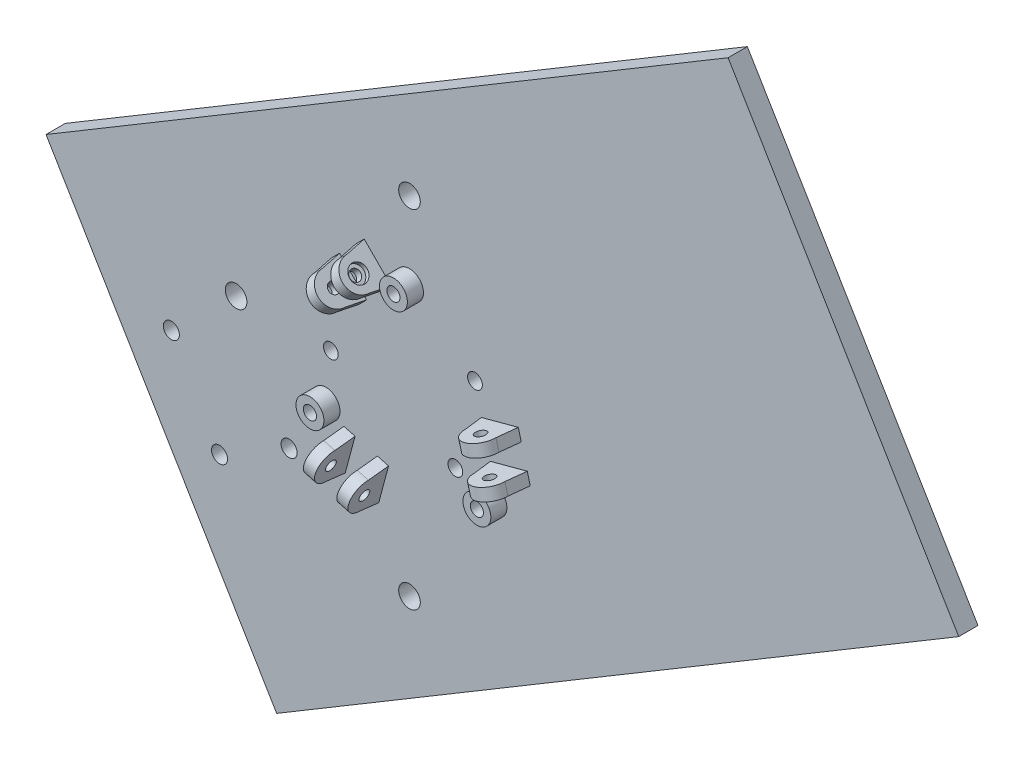
SolidWorks part; units mm, degrees
ref_plane "Front Plane" through (0, 0, 0) normal (0, 0, 1) x (1, 0, 0)
ref_plane "Top Plane" through (0, 0, 0) normal (0, 1, 0) x (1, 0, 0)
ref_plane "Right Plane" through (0, 0, 0) normal (1, 0, 0) x (0, 0, -1)
sketch "S01 - Rounded V3 backplate with cage and cassette fixings" plane through (0, 0, 0) normal (0, 0, 1) x (1, 0, 0)
  line L0 (-113.1634, 13.9297) -> (41.3567, 106.2526)
  line L5 (-113.1634, 13.9297) -> (-41.3567, -106.2526)
  line L7 (-41.3567, -106.2526) -> (113.1634, -13.9297)
  line L8 (-113.1634, 13.9297) -> (113.1634, -13.9297) construction
  line L9 (41.3567, 106.2526) -> (-41.3567, -106.2526) construction
  line L10 (41.3567, 106.2526) -> (99.1896, 140.8067)
  line L11 (99.1896, 140.8067) -> (170.9963, 20.6243)
  line L12 (170.9963, 20.6243) -> (113.1634, -13.9297)
  circle A7 centre (0, 54) radius 3.3651
  circle A8 centre (-53.9735, 0) radius 3.3651
  circle A9 centre (0, -54) radius 3.3651
  circle A10 centre (14.2762, -12.2367) radius 2.2944
  circle A11 centre (20.3946, 14.2762) radius 2.2944
  circle A12 centre (-24.4735, 0) radius 2.2944
  point P1 (0, 0)
  point P3 (0, 0)
  dimension "D2" = 180
  dimension "D3" = 54
  dimension "D4" = 6.7302
  dimension "D5" = 4.5888
  dimension "D6" = 20.3946
  dimension "D7" = 14.2762
  dimension "D8" = 4.5888
  dimension "D9" = 14.2762
  dimension "D10" = 12.2367
  dimension "D11" = 24.4735
  dimension "D12" = 4.5888
  dimension "D13" = 29.5
  dimension "D14" = 6.7302
  dimension "D16" = 6.7302
  dimension "D15" = 54
  dimension "D17" = 140
  dimension "D18" = 113.1634
  dimension "D19" = 106.2526
  dimension "D20" = 67.3693
extrude "01 - Rounded V3 backplate with cage and cassette fixings" add sketch "S01 - Rounded V3 backplate with cage and cassette fixings" along normal blind 6 from offset 12 offset against normal yes
sketch "S02 - Three cord guide pedestals" plane through (0, 0, 0) normal (0, 0, 1) x (1, 0, 0)
  circle A0 centre (25.9808, -15) radius 4.35
  circle A1 centre (0, 30) radius 4.35
  circle A2 centre (-25.9808, -15) radius 4.35
  dimension "D1" = 8.7
  dimension "D2" = 8.7
  dimension "D3" = 8.7
  dimension "D4" = 25.9808
  dimension "D5" = 25.9808
  dimension "D6" = 30
  dimension "D7" = 15
extrude "02 - Three cord guide pedestals" add sketch "S02 - Three cord guide pedestals" along normal blind 5 from offset 6 offset against normal yes
sketch "S03 - Three smooth grommet seats" plane through (0, 0, 0) normal (0, 0, 1) x (1, 0, 0)
  circle A0 centre (25.9808, -15) radius 2.05
  circle A1 centre (0, 30) radius 2.05
  circle A2 centre (-25.9808, -15) radius 2.05
  dimension "D1" = 4.1
  dimension "D2" = 4.1
  dimension "D3" = 4.1
  dimension "D4" = 25.9808
  dimension "D5" = 25.9808
  dimension "D6" = 30
  dimension "D7" = 15
extrude "03 - Three smooth grommet seats" cut sketch "S03 - Three smooth grommet seats" along normal blind 14 from offset 13 offset against normal yes
sketch3d "Plane points - Integral A1 fork cheek L"
  point P0 (30, 0, 0)
  point P1 (12.6133, -4.6587, 0)
  point P2 (30, 0, 18)
ref_plane "Drilling plane - Integral A1 fork cheek L" through (2.0096, -7.5, 0) normal (-0.2588, 0.9659, 0) x (0.9659, 0.2588, 0)
sketch "S04 - Integral A1 fork cheek L" plane through (2.0096, -7.5, 0) normal (-0.2588, 0.9659, 0) x (0.9659, 0.2588, 0)
  line L0 (35.0778, 7) -> (22.8778, 7)
  line L1 (22.8778, 7) -> (24.0278, 0)
  line L2 (33.9278, 0) -> (35.0778, 7)
  arc A0 (24.0278, 0) -> (33.9278, 0) centre (28.9778, 0) ccw
  dimension "D1" = 4.95
  dimension "D2" = 22.8778
  dimension "D3" = 28.9778
  dimension "D4" = 35.0778
  dimension "D5" = 7
extrude "04 - Integral A1 fork cheek L" add sketch "S04 - Integral A1 fork cheek L" along normal blind 3.6 from offset 7.2 offset against normal yes
sketch3d "Plane points - Integral A1 fork cheek R"
  point P0 (30, 0, 0)
  point P1 (12.6133, -4.6587, 0)
  point P2 (30, 0, 18)
ref_plane "Drilling plane - Integral A1 fork cheek R" through (2.0096, -7.5, 0) normal (-0.2588, 0.9659, 0) x (0.9659, 0.2588, 0)
sketch "S05 - Integral A1 fork cheek R" plane through (2.0096, -7.5, 0) normal (-0.2588, 0.9659, 0) x (0.9659, 0.2588, 0)
  line L0 (35.0778, 7) -> (22.8778, 7)
  line L1 (22.8778, 7) -> (24.0278, 0)
  line L2 (33.9278, 0) -> (35.0778, 7)
  arc A0 (24.0278, 0) -> (33.9278, 0) centre (28.9778, 0) ccw
  dimension "D1" = 4.95
  dimension "D2" = 22.8778
  dimension "D3" = 28.9778
  dimension "D4" = 35.0778
  dimension "D5" = 7
extrude "05 - Integral A1 fork cheek R" add sketch "S05 - Integral A1 fork cheek R" along normal blind 3.6 from offset 3.6
sketch3d "Plane points - A1 pivot through both cheeks"
  point P0 (30, 0, 0)
  point P1 (12.6133, -4.6587, 0)
  point P2 (30, 0, 18)
ref_plane "Drilling plane - A1 pivot through both cheeks" through (2.0096, -7.5, 0) normal (-0.2588, 0.9659, 0) x (0.9659, 0.2588, 0)
sketch "S06 - A1 pivot through both cheeks" plane through (2.0096, -7.5, 0) normal (-0.2588, 0.9659, 0) x (0.9659, 0.2588, 0)
  circle A0 centre (28.9778, 0) radius 1.65
  dimension "D1" = 3.3
  dimension "D2" = 28.9778
extrude "06 - A1 pivot through both cheeks" cut sketch "S06 - A1 pivot through both cheeks" along normal blind 15 from offset 7.5 offset against normal yes
sketch3d "Plane points - A1 recessed pivot screw head"
  point P0 (30, 0, 0)
  point P1 (12.6133, -4.6587, 0)
  point P2 (30, 0, 18)
ref_plane "Drilling plane - A1 recessed pivot screw head" through (2.0096, -7.5, 0) normal (-0.2588, 0.9659, 0) x (0.9659, 0.2588, 0)
sketch "S07 - A1 recessed pivot screw head" plane through (2.0096, -7.5, 0) normal (-0.2588, 0.9659, 0) x (0.9659, 0.2588, 0)
  circle A0 centre (28.9778, 0) radius 2.7
  dimension "D1" = 5.4
  dimension "D2" = 28.9778
extrude "07 - A1 recessed pivot screw head" cut sketch "S07 - A1 recessed pivot screw head" along normal blind 1.5 from offset 7.3 offset against normal yes
sketch3d "Plane points - Integral A2 fork cheek L"
  point P0 (-15, 25.9808, 0)
  point P1 (-2.2721, 13.2528, 0)
  point P2 (-15, 25.9808, 18)
ref_plane "Drilling plane - Integral A2 fork cheek L" through (5.4904, 5.4904, 0) normal (-0.7071, -0.7071, 0) x (-0.7071, 0.7071, 0)
sketch "S08 - Integral A2 fork cheek L" plane through (5.4904, 5.4904, 0) normal (-0.7071, -0.7071, 0) x (-0.7071, 0.7071, 0)
  line L0 (35.0778, 7) -> (22.8778, 7)
  line L1 (22.8778, 7) -> (24.0278, 0)
  line L2 (33.9278, 0) -> (35.0778, 7)
  arc A0 (24.0278, 0) -> (33.9278, 0) centre (28.9778, 0) ccw
  dimension "D1" = 4.95
  dimension "D2" = 22.8778
  dimension "D3" = 28.9778
  dimension "D4" = 35.0778
  dimension "D5" = 7
extrude "08 - Integral A2 fork cheek L" add sketch "S08 - Integral A2 fork cheek L" along normal blind 3.6 from offset 7.2 offset against normal yes
sketch3d "Plane points - Integral A2 fork cheek R"
  point P0 (-15, 25.9808, 0)
  point P1 (-2.2721, 13.2528, 0)
  point P2 (-15, 25.9808, 18)
ref_plane "Drilling plane - Integral A2 fork cheek R" through (5.4904, 5.4904, 0) normal (-0.7071, -0.7071, 0) x (-0.7071, 0.7071, 0)
sketch "S09 - Integral A2 fork cheek R" plane through (5.4904, 5.4904, 0) normal (-0.7071, -0.7071, 0) x (-0.7071, 0.7071, 0)
  line L0 (35.0778, 7) -> (22.8778, 7)
  line L1 (22.8778, 7) -> (24.0278, 0)
  line L2 (33.9278, 0) -> (35.0778, 7)
  arc A0 (24.0278, 0) -> (33.9278, 0) centre (28.9778, 0) ccw
  dimension "D1" = 4.95
  dimension "D2" = 22.8778
  dimension "D3" = 28.9778
  dimension "D4" = 35.0778
  dimension "D5" = 7
extrude "09 - Integral A2 fork cheek R" add sketch "S09 - Integral A2 fork cheek R" along normal blind 3.6 from offset 3.6
sketch3d "Plane points - A2 pivot through both cheeks"
  point P0 (-15, 25.9808, 0)
  point P1 (-2.2721, 13.2528, 0)
  point P2 (-15, 25.9808, 18)
ref_plane "Drilling plane - A2 pivot through both cheeks" through (5.4904, 5.4904, 0) normal (-0.7071, -0.7071, 0) x (-0.7071, 0.7071, 0)
sketch "S10 - A2 pivot through both cheeks" plane through (5.4904, 5.4904, 0) normal (-0.7071, -0.7071, 0) x (-0.7071, 0.7071, 0)
  circle A0 centre (28.9778, 0) radius 1.65
  dimension "D1" = 3.3
  dimension "D2" = 28.9778
extrude "10 - A2 pivot through both cheeks" cut sketch "S10 - A2 pivot through both cheeks" along normal blind 15 from offset 7.5 offset against normal yes
sketch3d "Plane points - A2 recessed pivot screw head"
  point P0 (-15, 25.9808, 0)
  point P1 (-2.2721, 13.2528, 0)
  point P2 (-15, 25.9808, 18)
ref_plane "Drilling plane - A2 recessed pivot screw head" through (5.4904, 5.4904, 0) normal (-0.7071, -0.7071, 0) x (-0.7071, 0.7071, 0)
sketch "S11 - A2 recessed pivot screw head" plane through (5.4904, 5.4904, 0) normal (-0.7071, -0.7071, 0) x (-0.7071, 0.7071, 0)
  circle A0 centre (28.9778, 0) radius 2.7
  dimension "D1" = 5.4
  dimension "D2" = 28.9778
extrude "11 - A2 recessed pivot screw head" cut sketch "S11 - A2 recessed pivot screw head" along normal blind 1.5 from offset 7.3 offset against normal yes
sketch3d "Plane points - Integral A3 fork cheek L"
  point P0 (-15, -25.9808, 0)
  point P1 (-10.3413, -8.5941, 0)
  point P2 (-15, -25.9808, 18)
ref_plane "Drilling plane - Integral A3 fork cheek L" through (-7.5, 2.0096, 0) normal (0.9659, -0.2588, 0) x (0, 0, -1)
sketch "S12 - Integral A3 fork cheek L" plane through (-7.5, 2.0096, 0) normal (0.9659, -0.2588, 0) x (0, 0, -1)
  line L0 (7, -35.0778) -> (7, -22.8778)
  line L1 (7, -22.8778) -> (0, -24.0278)
  line L2 (0, -33.9278) -> (7, -35.0778)
  arc A0 (0, -24.0278) -> (0, -33.9278) centre (0, -28.9778) ccw
  dimension "D1" = 4.95
  dimension "D2" = 7
  dimension "D3" = 22.8778
  dimension "D4" = 28.9778
  dimension "D5" = 35.0778
extrude "12 - Integral A3 fork cheek L" add sketch "S12 - Integral A3 fork cheek L" along normal blind 3.6 from offset 7.2 offset against normal yes
sketch3d "Plane points - Integral A3 fork cheek R"
  point P0 (-15, -25.9808, 0)
  point P1 (-10.3413, -8.5941, 0)
  point P2 (-15, -25.9808, 18)
ref_plane "Drilling plane - Integral A3 fork cheek R" through (-7.5, 2.0096, 0) normal (0.9659, -0.2588, 0) x (0, 0, -1)
sketch "S13 - Integral A3 fork cheek R" plane through (-7.5, 2.0096, 0) normal (0.9659, -0.2588, 0) x (0, 0, -1)
  line L0 (7, -35.0778) -> (7, -22.8778)
  line L1 (7, -22.8778) -> (0, -24.0278)
  line L2 (0, -33.9278) -> (7, -35.0778)
  arc A0 (0, -24.0278) -> (0, -33.9278) centre (0, -28.9778) ccw
  dimension "D1" = 4.95
  dimension "D2" = 7
  dimension "D3" = 22.8778
  dimension "D4" = 28.9778
  dimension "D5" = 35.0778
extrude "13 - Integral A3 fork cheek R" add sketch "S13 - Integral A3 fork cheek R" along normal blind 3.6 from offset 3.6
sketch3d "Plane points - A3 pivot through both cheeks"
  point P0 (-15, -25.9808, 0)
  point P1 (-10.3413, -8.5941, 0)
  point P2 (-15, -25.9808, 18)
ref_plane "Drilling plane - A3 pivot through both cheeks" through (-7.5, 2.0096, 0) normal (0.9659, -0.2588, 0) x (0, 0, -1)
sketch "S14 - A3 pivot through both cheeks" plane through (-7.5, 2.0096, 0) normal (0.9659, -0.2588, 0) x (0, 0, -1)
  circle A0 centre (0, -28.9778) radius 1.65
  dimension "D1" = 3.3
  dimension "D2" = 28.9778
extrude "14 - A3 pivot through both cheeks" cut sketch "S14 - A3 pivot through both cheeks" along normal blind 15 from offset 7.5 offset against normal yes
sketch3d "Plane points - A3 recessed pivot screw head"
  point P0 (-15, -25.9808, 0)
  point P1 (-10.3413, -8.5941, 0)
  point P2 (-15, -25.9808, 18)
ref_plane "Drilling plane - A3 recessed pivot screw head" through (-7.5, 2.0096, 0) normal (0.9659, -0.2588, 0) x (0, 0, -1)
sketch "S15 - A3 recessed pivot screw head" plane through (-7.5, 2.0096, 0) normal (0.9659, -0.2588, 0) x (0, 0, -1)
  circle A0 centre (0, -28.9778) radius 2.7
  dimension "D1" = 5.4
  dimension "D2" = 28.9778
extrude "15 - A3 recessed pivot screw head" cut sketch "S15 - A3 recessed pivot screw head" along normal blind 1.5 from offset 7.3 offset against normal yes
sketch "Sketch1" plane through (0, 0, -12) normal (0, 0, -1) x (-1, 0, 0)
  line L0 (-18.8004, 31.6168) -> (-16.8004, 35.0809)
  line L1 (7.1804, -13.3832) -> (9.1804, -9.9191)
  line L2 (7.1804, -13.3832) -> (15.8406, -18.3832)
  line L3 (15.8406, -18.3832) -> (17.8406, -14.9191)
  line L4 (9.1804, -9.9191) -> (17.8406, -14.9191)
  line L5 (0, 0) -> (25.9808, -15) construction
  line L6 (15.1804, 0.4732) -> (23.8406, -4.5268)
  line L7 (15.1804, 0.4732) -> (13.1804, -2.9909)
  line L8 (13.1804, -2.9909) -> (21.8406, -7.9909)
  line L9 (23.8406, -4.5268) -> (21.8406, -7.9909)
  line L10 (-44.7811, -13.3832) -> (-42.7811, -9.9191)
  line L11 (-44.7811, -13.3832) -> (-36.1209, -18.3832)
  line L12 (-36.1209, -18.3832) -> (-34.1209, -14.9191)
  line L13 (-42.7811, -9.9191) -> (-34.1209, -14.9191)
  line L14 (-36.7811, 0.4732) -> (-28.1209, -4.5268)
  line L15 (-36.7811, 0.4732) -> (-38.7811, -2.9909)
  line L16 (-38.7811, -2.9909) -> (-30.1209, -7.9909)
  line L17 (-28.1209, -4.5268) -> (-30.1209, -7.9909)
  line L18 (0, 0) -> (-15.04, -26.05) construction
  line L19 (-25.9808, -15) -> (-12.9904, -22.5) construction
  line L20 (-18.8004, 31.6168) -> (-10.1401, 26.6168)
  line L21 (-10.1401, 26.6168) -> (-8.1401, 30.0809)
  line L22 (-16.8004, 35.0809) -> (-8.1401, 30.0809)
  line L23 (-10.8004, 45.4732) -> (-2.1401, 40.4732)
  line L24 (-10.8004, 45.4732) -> (-12.8004, 42.0091)
  line L25 (-12.8004, 42.0091) -> (-4.1401, 37.0091)
  line L26 (-2.1401, 40.4732) -> (-4.1401, 37.0091)
  line L27 (0, 0) -> (26.3488, 45.6375) construction
  line L28 (0, 30) -> (12.9904, 22.5) construction
  dimension "D1" = 10
  dimension "D2" = 4
  dimension "D3" = 4
  dimension "D4" = 7.09
  dimension "D5" = 4
  dimension "D6" = 10
  dimension "D7" = 8
  dimension "D8" = 7.09
  dimension "D9" = 4
  dimension "D10" = 10
  dimension "D11" = 8
  dimension "D12" = 7.09
extrude "Boss-Extrude1" add sketch "Sketch1" along normal blind 20
sketch "Sketch2" plane through (-16.9904, 29.4282, 0) normal (-0.5, 0.866, 0) x (0.866, 0.5, 0)
  line L0 (27.09, 32) -> (27.09, 12) construction
  line L1 (22.09, 32) -> (32.09, 32) construction
  line L2 (22.09, 12) -> (32.09, 12) construction
  line L3 (-17.91, 32) -> (-17.91, 12) construction
  line L4 (-22.91, 32) -> (-12.91, 32) construction
  line L5 (-22.91, 12) -> (-12.91, 12) construction
  circle A0 centre (27.09, 27) radius 2.2
  circle A1 centre (-17.91, 27) radius 2.2
  point P10 (0, 0)
  point P17 (0, 0)
  dimension "D1" = 4.4
  dimension "D2" = 4.4
  dimension "D3" = 15
  dimension "D4" = 15
extrude "Cut-Extrude1" cut sketch "Sketch2" against normal through all both and the other way through all
fillet "Fillet1" radius 2 12 edges at (43.7811, -11.6512, -32) (35.1209, -16.6512, -32) (29.1209, -6.2588, -32) (37.7811, -1.2588, -32) (9.1401, 28.3488, -32) (17.8004, 33.3488, -32) (11.8004, 43.7412, -32) (3.1401, 38.7412, -32) (-8.1804, -11.6512, -32) (-16.8406, -16.6512, -32) (-14.1804, -1.2588, -32) (-22.8406, -6.2588, -32)
sketch "Sketch3" plane through (0, 0, -12) normal (0, 0, -1) x (-1, 0, 0)
  line L0 (-41.0491, -10.9191) -> (-43.0491, -14.3832) construction
  line L1 (24.9609, -38.5727) -> (59.6019, -58.5727)
  line L2 (24.9609, -38.5727) -> (49.9609, 4.7286)
  line L3 (49.9609, 4.7286) -> (84.6019, -15.2714)
  line L4 (59.6019, -58.5727) -> (84.6019, -15.2714)
  line L5 (-31.8529, -6.9909) -> (-29.8529, -3.5268) construction
  line L6 (-29.8529, -3.5268) -> (-35.0491, -0.5268) construction
  dimension "D1" = 40
  dimension "D2" = 50
  dimension "D3" = 64.9931
  dimension "D4" = 2.9437
extrude "Boss-Extrude2" add sketch "Sketch3" along normal blind 10
sketch "Sketch4" plane through (0, 0, -22) normal (0, 0, -1) x (-1, 0, 0)
  circle A0 centre (74.1385, -19.3635) radius 2.5
  circle A1 centre (59.1385, -45.3442) radius 2.5
  circle A2 centre (37.4879, -32.8442) radius 2.5
  dimension "D1" = 5
  dimension "D3" = 5
  dimension "D4" = 5
extrude "Cut-Extrude3" cut sketch "Sketch4" against normal through all both and the other way through all
